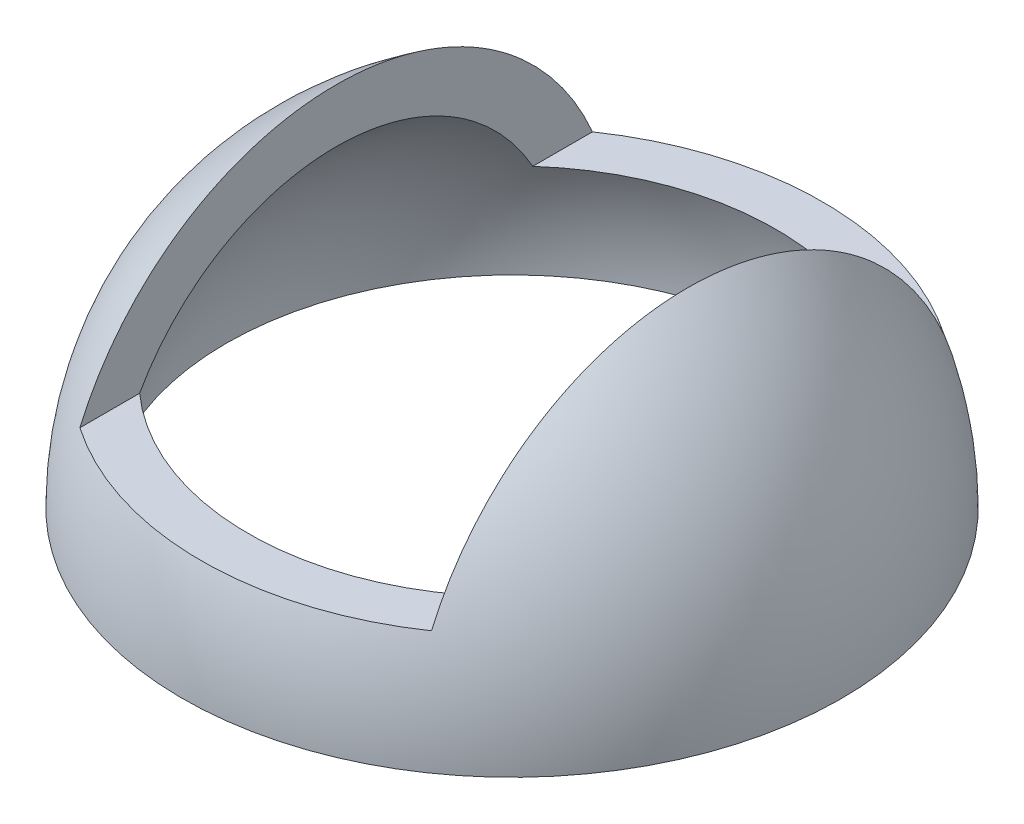
SolidWorks part; units mm, degrees
ref_plane "Front Plane" through (0, 0, 0) normal (0, 0, 1) x (1, 0, 0)
ref_plane "Top Plane" through (0, 0, 0) normal (0, 1, 0) x (1, 0, 0)
ref_plane "Right Plane" through (0, 0, 0) normal (1, 0, 0) x (0, 0, -1)
sketch "Sketch1" plane through (0, 0, 0) normal (0, 0, 1) x (1, 0, 0)
  line L0 (16.51, 0) -> (19.05, 0) construction
  line L1 (19.05, 0) -> (16.51, 0) construction
  line L2 (19.05, 0) -> (16.51, 0)
  line L3 (0, 19.05) -> (0, 16.51)
  arc A0 (19.05, 0) -> (0, 19.05) centre (0, 0) ccw
  arc A2 (16.51, 0) -> (0, 16.51) centre (0, 0) ccw
  circle A3 centre (0, 0) radius 19.05 construction
  circle A4 centre (0, 0) radius 16.51 construction
  dimension "D1" = 38.1
  dimension "D2" = 2.54
revolve "Revolve1" add sketch "Sketch1" angle 360 about L3
sketch "Sketch2" plane through (0, 0, 0) normal (0, 0, 1) x (1, 0, 0)
  line L0 (0, 6.35) -> (0, 0) construction
  line L1 (-10.16, 22.7688) -> (10.16, 22.7688)
  line L2 (-10.16, 22.7688) -> (-10.16, 6.35)
  line L3 (-10.16, 6.35) -> (10.16, 6.35)
  line L4 (10.16, 22.7688) -> (10.16, 6.35)
  dimension "D1" = 6.35
  dimension "D2" = 20.32
extrude "Cut-Extrude1" cut sketch "Sketch2" against normal mid plane 127
